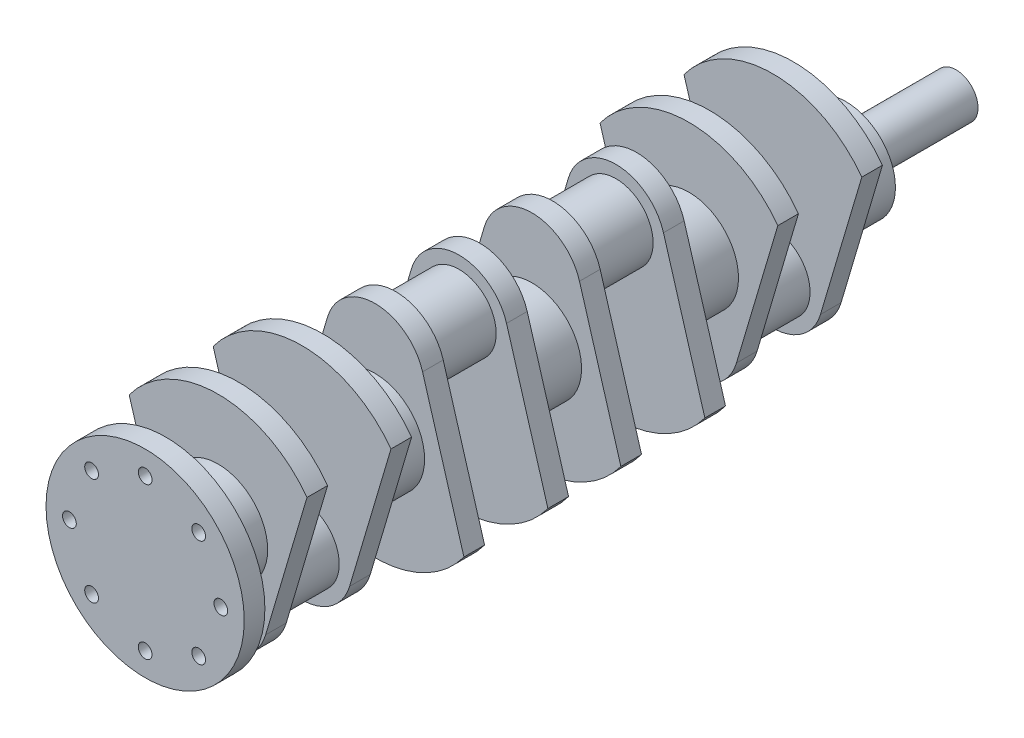
SolidWorks part; units mm, degrees
material "Cast Alloy Steel"
ref_plane "Front Plane" through (0, 0, 0) normal (0, 0, 1) x (1, 0, 0)
ref_plane "Top Plane" through (0, 0, 0) normal (0, 1, 0) x (1, 0, 0)
ref_plane "Right Plane" through (0, 0, 0) normal (1, 0, 0) x (0, 0, -1)
sketch "Sketch2" plane through (0, 0, 0) normal (0, 0, 1) x (1, 0, 0)
  line L0 (0, -68.2947) -> (0, 68.2947) construction
  line L1 (-64.5699, 47.2306) -> (-34.5175, -54.2246)
  line L2 (64.5699, 47.2306) -> (34.5175, -54.2246)
  arc A0 (-34.5175, -54.2246) -> (34.5175, -54.2246) centre (0, -44) ccw
  arc A1 (-64.5699, 47.2306) -> (64.5699, 47.2306) centre (0, 0) cw
  point P4 (0, 0)
  dimension "D1" = 72
  dimension "D3" = 44
  dimension "D4" = 80
  dimension "D2" = 33
extrude "Boss-Extrude1" add sketch "Sketch2" along normal blind 15
sketch "Sketch3" plane through (0, 0, 15) normal (0, 0, 1) x (1, 0, 0)
  circle A0 centre (0, 0) radius 36
  dimension "D1" = 36
extrude "Boss-Extrude2" add sketch "Sketch3" along normal blind 38
sketch "Sketch4" plane through (0, 0, 0) normal (0, 0, -1) x (-1, 0, 0)
  circle A0 centre (0, -44) radius 27
  dimension "D1" = 54
extrude "Boss-Extrude3" add sketch "Sketch4" along normal blind 46
ref_plane "Plane1" through (0, 0, -23) normal (0, 0, -1) x (-1, 0, 0)
mirror "Mirror2" about plane through (0, 0, -23) normal (0, 0, -1) of "Boss-Extrude1", "Boss-Extrude2"
ref_plane "Plane2" through (0, 0, -80) normal (0, 0, -1) x (-1, 0, 0)
mirror "Mirror6" about plane through (0, 0, -80) normal (0, 0, -1) of bodies 105
move or copy body "Body-Move/Copy3" bodies to move or copy 105 copy no rotation origin (0, 0, 0) rotation axis (0, 0, 1) rotation angle 180
ref_plane "Plane3" through (0, 0, 34) normal (0, 0, 1) x (1, 0, 0)
mirror "Mirror7" about plane through (0, 0, 34) normal (0, 0, 1) of bodies 109 112
sketch "Sketch5" plane through (0, 0, -213) normal (0, 0, -1) x (-1, 0, 0)
  circle A0 centre (0, 0) radius 16
  point P4 (0, 0)
  dimension "D1" = 32
extrude "Boss-Extrude4" add sketch "Sketch5" along normal blind 80
sketch "Sketch6" plane through (0, 0, 281) normal (0, 0, 1) x (1, 0, 0)
  circle A0 centre (0, 0) radius 72
  circle A1 centre (0, 0) radius 55 construction
  circle A2 centre (0, 55) radius 5
  circle A3 centre (38.8909, 38.8909) radius 5
  circle A4 centre (55, 0) radius 5
  circle A5 centre (38.8909, -38.8909) radius 5
  circle A6 centre (0, -55) radius 5
  circle A7 centre (-38.8909, -38.8909) radius 5
  circle A8 centre (-55, 0) radius 5
  circle A9 centre (-38.8909, 38.8909) radius 5
  point P22 (0, 0)
  dimension "D1" = 72
  dimension "D2" = 55
  dimension "D3" = 10
  dimension "D4" = 8
extrude "Boss-Extrude5" add sketch "Sketch6" along normal blind 15
combine bodies "Combine1" operation type add bodies to combine 116 114 112 115
sketch "Sketch9" plane through (0, 0, -293) normal (0, 0, -1) x (-1, 0, 0)
  point P0 (0, 0)
  point P1 (0, 0)
  point P3 (0, 0)
  point P5 (-75.948, 10.7466)
